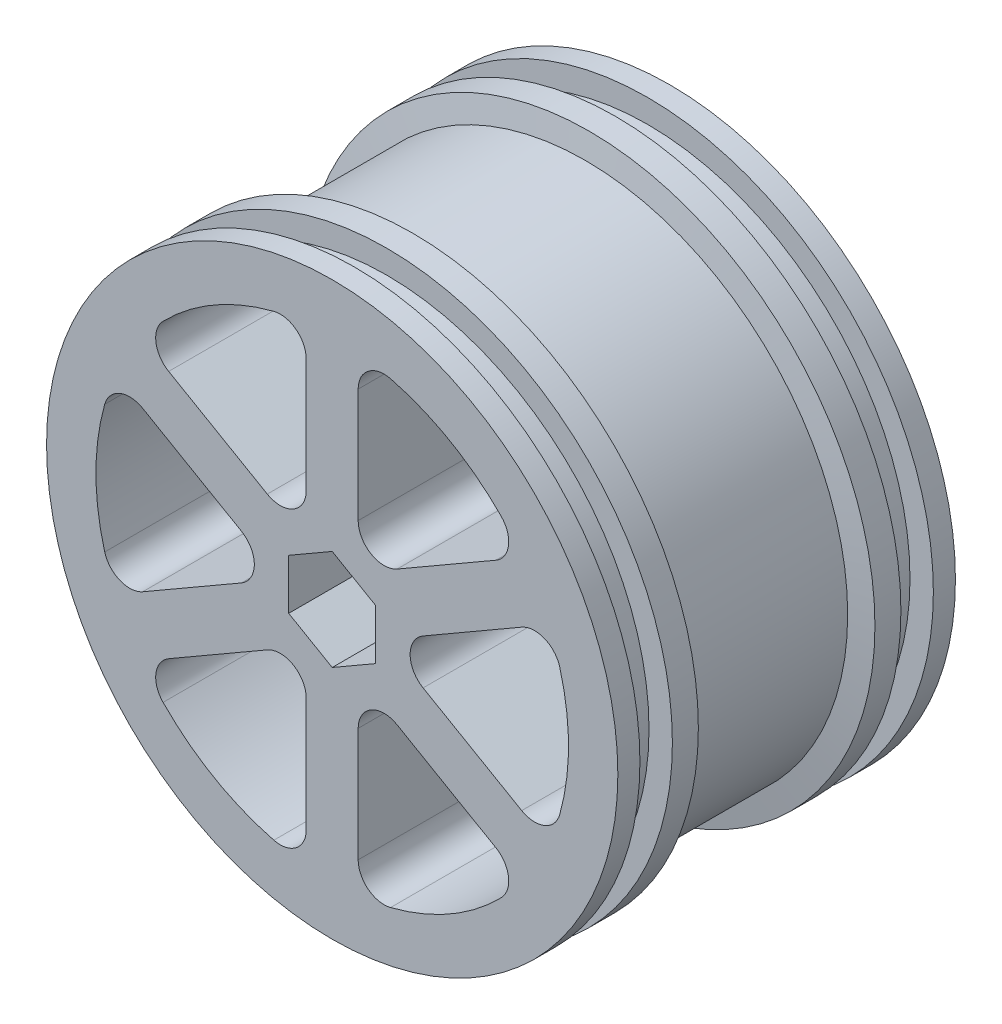
SolidWorks part; units mm, degrees
note: '?' marks a value the reader was unsure of.
ref_plane "Front Plane" through (0, 0, 0) normal (0, 0, 1) x (1, 0, 0)
ref_plane "Top Plane" through (0, 0, 0) normal (0, 1, 0) x (1, 0, 0)
ref_plane "Right Plane" through (0, 0, 0) normal (1, 0, 0) x (0, 0, -1)
sketch "Sketch1" plane through (0, 0, 0) normal (1, 0, 0) x (0, 0, -1)
  line L1 (0, 22) -> (1.7, 22)
  line L2 (1.7, 22) -> (1.7, 20.2)
  line L3 (1.7, 20.2) -> (4.2, 20.2)
  line L4 (4.2, 20.2) -> (4.2, 22)
  line L5 (4.2, 22) -> (6.2, 22)
  line L6 (6.2, 22) -> (6.5, 20.2)
  line L7 (19.8, 22) -> (19.5, 20.2)
  line L8 (19.5, 20.2) -> (6.5, 20.2)
  line L10 (0, 18.2) -> (26, 18.2)
  line L11 (19.8, 22) -> (21.8, 22)
  line L12 (21.8, 22) -> (21.8, 20.2)
  line L13 (21.8, 20.2) -> (24.3, 20.2)
  line L14 (24.3, 20.2) -> (24.3, 22)
  line L15 (24.3, 22) -> (26, 22)
  line L18 (-0.3222, 0) -> (27.2819, 0) construction
  line L19 (0, 0) -> (0, 18.2) construction
  line L20 (0, 22) -> (0, 1028.7814) construction
  line L21 (0, 22) -> (0, 18.2)
  line L22 (26, 22) -> (26, 18.2)
  dimension "D1" = 22
  dimension "D2" = 1.7
  dimension "D3" = 2
  dimension "D4" = 0.3
  dimension "D5" = 2.3
  dimension "D6" = 3.8
  dimension "D7" = 1.8
  dimension "D8" = 2.5
  dimension "D9" = 26
revolve "Revolve1" add sketch "Sketch1" angle 360 about L18
sketch "Sketch2" plane through (0, 0, 0) normal (0, 0, 1) x (1, 0, 0)
  line L0 (0, 0) -> (0, 18.2) construction
  line L1 (-2, 18.2) -> (-2, 0)
  line L2 (-2, 18.2) -> (2, 18.2)
  line L3 (-2, 0) -> (2, 0)
  line L4 (2, 18.2) -> (2, 0)
  line L5 (-2, 18.2) -> (2, 0) construction
  line L6 (-2, 0) -> (2, 18.2) construction
  circle A0 centre (0, 0) radius 18.2 construction
  point P6 (0, 9.1)
  dimension "D1" = 18.2
  dimension "D2" = 4
extrude "Boss-Extrude1" add sketch "Sketch2" against normal blind 24
pattern_circular "CirPattern1" count 6 over 360 about axis through (0, 0, 0) along (0, 0, 1) of "Boss-Extrude1"
sketch "Sketch3" plane through (0, 0, 0) normal (0, 0, 1) x (1, 0, 0)
  line L5 (0, -3.87) -> (3.3515, -1.935)
  line L6 (3.3515, -1.935) -> (3.3515, 1.935)
  line L7 (3.3515, 1.935) -> (0, 3.87)
  line L8 (0, 3.87) -> (-3.3515, 1.935)
  line L9 (-3.3515, 1.935) -> (-3.3515, -1.935)
  line L10 (-3.3515, -1.935) -> (0, -3.87)
  circle A0 centre (0, 0) radius 3.3515 construction
  dimension "D1" = 3.87
extrude "Cut-Extrude1" cut sketch "Sketch3" against normal through all both and the other way through all
fillet "Fillet1" radius 2 18 edges at (14.6662, 10.7769, -12) (-14.6662, 10.7769, -12) (-2, 18.0898, -12) (2, 18.0898, -12) (-16.6662, 7.3128, -12) (-14.6662, -10.7769, -12) (-16.6662, -7.3128, -12) (2, -18.0898, -12) (-2, -18.0898, -12) (14.6662, -10.7769, -12) (16.6662, -7.3128, -12) (16.6662, 7.3128, -12) (4, 0, -12) (2, -3.4641, -12) (-2, -3.4641, -12) (-4, 0, -12) (2, 3.4641, -12) (-2, 3.4641, -12)
fillet "Fillet2" radius 2 1 edges at (18.2, 0, -26)
sketch "Sketch4" plane through (0, 0, 0) normal (1, 0, 0) x (0, 0, -1)
  line L0 (0, 0) -> (26, 0) construction
  line L1 (26, -22) -> (26, 22) construction
ref_axis "Axis1" through (0, 0, 0) along (0, 0, -1)?
